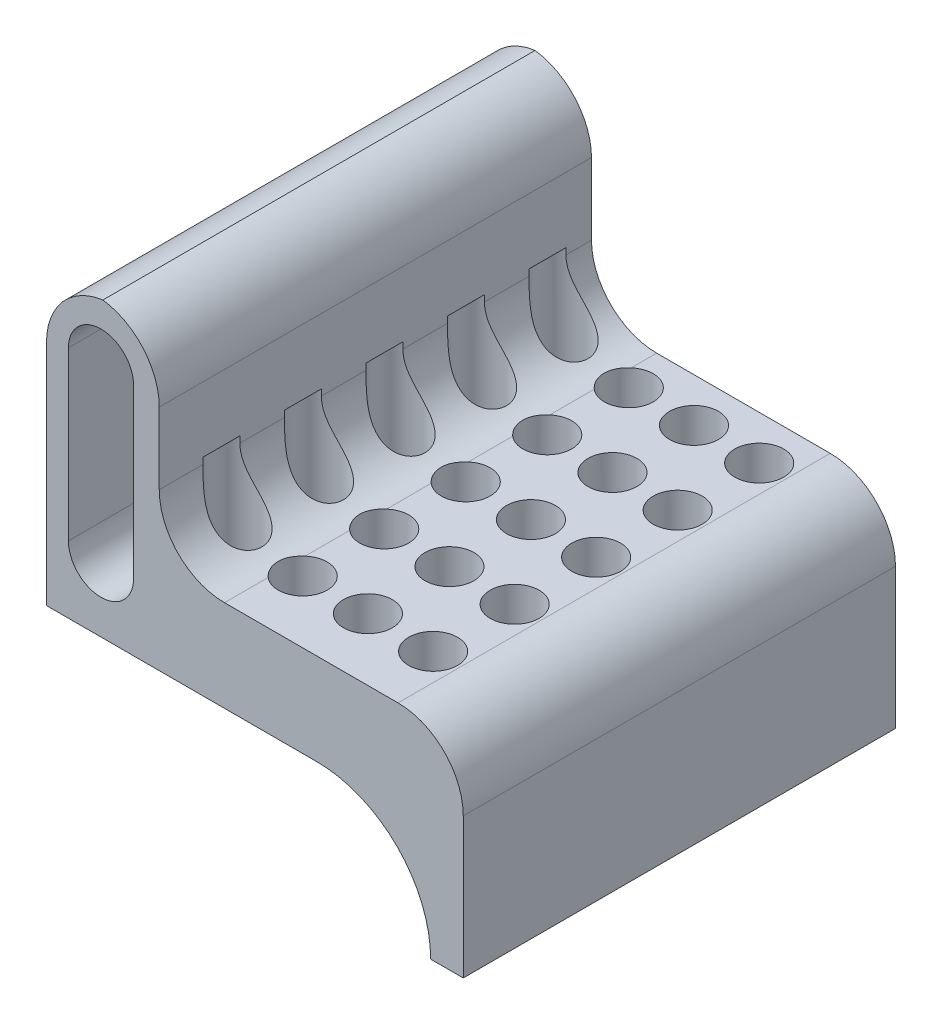
SolidWorks part; units mm, degrees
ref_plane "Plan de face" through (0, 0, 0) normal (0, 0, 1) x (1, 0, 0)
ref_plane "Plan de dessus" through (0, 0, 0) normal (0, 1, 0) x (1, 0, 0)
ref_plane "Plan de droite" through (0, 0, 0) normal (1, 0, 0) x (0, 0, -1)
sketch "Esquisse1" plane through (0, 0, 0) normal (0, 0, 1) x (1, 0, 0)
  line L0 (30, 18) -> (30, 0) construction
  line L1 (6.4395, 0) -> (23, 0)
  line L2 (6.4395, 0) -> (6.4395, 18)
  line L3 (6.4395, 18) -> (13.3537, 18)
  line L5 (23, 18) -> (23, 0) construction
  line L6 (23, 0) -> (23, -7) construction
  line L7 (23, -7) -> (30, -7) construction
  line L8 (30, -7) -> (32, -7)
  line L9 (32, -7) -> (32, 5.6129)
  line L10 (9.7815, 14.3649) -> (9.7815, 4.1123) construction
  line L11 (11.7815, 14.3649) -> (11.7815, 4.1123)
  line L12 (7.7815, 14.3649) -> (7.7815, 4.1123)
  line L13 (13.3537, 18) -> (13.3537, 5.6129)
  line L14 (13.3537, 5.6129) -> (32, 5.6129)
  arc A0 (23, 0) -> (30, -7) centre (23, -7) cw
  arc A1 (11.7815, 14.3649) -> (7.7815, 14.3649) centre (9.7815, 14.3649) ccw
  arc A2 (7.7815, 4.1123) -> (11.7815, 4.1123) centre (9.7815, 4.1123) ccw
  point P15 (9.7815, 9.2386)
  dimension "D5" = 7
  dimension "D1" = 18
  dimension "D4" = 7
  dimension "D6" = 7
extrude "Boss.-Extru.1" add sketch "Esquisse1" along normal blind 26.51
fillet "Congé1" radius 4 4 edges at (13.3537, 5.6129, 13.255) (32, 5.6129, 13.255) (6.4395, 18, 13.255) (13.3537, 18, 13.255)
sketch "Esquisse2" plane through (0, 0, 0) normal (0, -1, 0) x (1, 0, 0)
  circle A0 centre (14.3382, 2.696) radius 1.5
  circle A1 centre (18.3382, 2.696) radius 1.5
  circle A2 centre (22.3382, 2.696) radius 1.5
  circle A3 centre (26.3382, 2.696) radius 1.5
  circle A4 centre (18.3382, 7.696) radius 1.5
  circle A5 centre (22.3382, 7.696) radius 1.5
  circle A6 centre (26.3382, 7.696) radius 1.5
  circle A7 centre (18.3382, 12.696) radius 1.5
  circle A8 centre (22.3382, 12.696) radius 1.5
  circle A9 centre (26.3382, 12.696) radius 1.5
  circle A10 centre (18.3382, 17.696) radius 1.5
  circle A11 centre (22.3382, 17.696) radius 1.5
  circle A12 centre (26.3382, 17.696) radius 1.5
  circle A13 centre (18.3382, 22.696) radius 1.5
  circle A14 centre (22.3382, 22.696) radius 1.5
  circle A15 centre (26.3382, 22.696) radius 1.5
  circle A16 centre (14.3382, 7.696) radius 1.5
  circle A17 centre (14.3382, 12.696) radius 1.5
  circle A18 centre (14.3382, 17.696) radius 1.5
  circle A19 centre (14.3382, 22.696) radius 1.5
  dimension "D2" = 4
  dimension "D1" = 5
extrude "Enlèv. mat.-Extru.1" cut sketch "Esquisse2" against normal blind 10 and the other way blind 10
